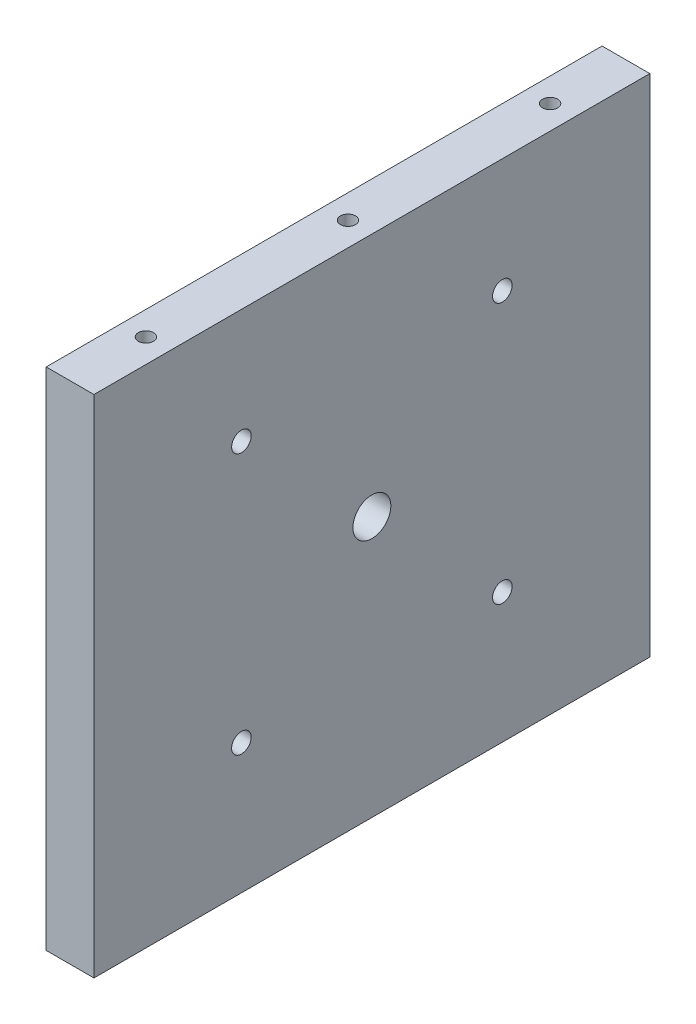
SolidWorks part; units mm, degrees
ref_plane "Front Plane" through (0, 0, 0) normal (0, 0, 1) x (1, 0, 0)
ref_plane "Top Plane" through (0, 0, 0) normal (0, 1, 0) x (1, 0, 0)
ref_plane "Right Plane" through (0, 0, 0) normal (1, 0, 0) x (0, 0, -1)
sketch "Sketch1" plane through (0, 0, 0) normal (1, 0, 0) x (0, 0, -1)
  line L1 (-69.85, -63.5) -> (69.85, -63.5)
  line L2 (-69.85, -63.5) -> (-69.85, 63.5)
  line L3 (-69.85, 63.5) -> (69.85, 63.5)
  line L4 (69.85, -63.5) -> (69.85, 63.5)
  line L5 (-69.85, -63.5) -> (69.85, 63.5) construction
  line L6 (-69.85, 63.5) -> (69.85, -63.5) construction
  point P0 (0, 0)
  dimension "D1" = 139.7
  dimension "D2" = 127
extrude "Boss-Extrude1" add sketch "Sketch1" along normal blind 12
sketch "Sketch2" plane through (0, 0, 0) normal (-1, 0, 0) x (0, 0, 1)
  line L0 (-69.85, 1.97) -> (69.85, 1.97) construction
  line L1 (-32.7869, -30.8169) -> (32.7869, -30.8169)
  line L2 (-32.7869, -30.8169) -> (-32.7869, 34.7569)
  line L3 (-32.7869, 34.7569) -> (32.7869, 34.7569)
  line L4 (32.7869, -30.8169) -> (32.7869, 34.7569)
  line L5 (-32.7869, -30.8169) -> (32.7869, 34.7569) construction
  line L6 (-32.7869, 34.7569) -> (32.7869, -30.8169) construction
  line L7 (-69.85, -63.5) -> (-69.85, 63.5) construction
  line L8 (69.85, 63.5) -> (69.85, -63.5) construction
  circle A0 centre (0, 1.97) radius 43.18
  circle A1 centre (0, 1.97) radius 4.7625
  point P0 (0, -43.7423)
  point P6 (0, 1.97)
  point P7 (-32.7869, 34.7569)
  point P8 (32.7869, 34.7569)
  point P9 (32.7869, -30.8169)
  point P10 (-32.7869, -30.8169)
  dimension "D2" = 86.36
  dimension "D4" = 65.47
  dimension "D5" = 9.525
  dimension "D1" = 92.7354
  dimension "D3" = 90
hole_wizard "#8 Clearance Hole1" positions "Sketch3" profile "Sketch4" hole size "#8" standard "ANSI Inch" end condition through all
sketch "Sketch3" plane through (0, 0, 0) normal (-1, 0, 0) x (0, 0, 1)
  point P0 (-32.7869, 34.7569)
  point P3 (32.7869, 34.7569)
  point P6 (32.7869, -30.8169)
  point P9 (-32.7869, -30.8169)
sketch "Sketch4" plane through (0, 34.7569, -32.7869) normal (0, 1, 0) x (0, 0, 1)
  line L0 (0, 0) -> (0, 12)
  line L1 (0, 12) -> (2.4574, 12)
  line L2 (2.4574, 12) -> (2.4574, 0)
  line L5 (2.4574, 0) -> (0, 0)
  line L11 (0, -6.35) -> (0, 107.95) construction
  dimension "Thru Hole Dia." = 4.9149
  dimension "Thru Hole Depth" = 12
extrude "Cut-Extrude1" cut sketch "Sketch2" against normal blind 1.27 contours L2 A0 | L4 A0 L3 L2 L1 | L3 A0 | L4 A0 | L1 A0 region at (0, -27.9071, -29.8771) region at (0, -35.0203, 0) region at (0, 1.97, -36.9903) region at (0, 1.97, 36.9903) region at (0, 38.9603, 0)
extrude "Cut-Extrude2" cut sketch "Sketch2<4>" against normal through all contours A1 region at (0, 1.97, 0)
sketch "Sketch2<4>" plane through (0, 0, 0) normal (-1, 0, 0) x (0, 0, 1) same geometry as "Sketch2"
sketch "Sketch5" plane through (0, -63.5, 0) normal (0, -1, 0) x (1, 0, 0)
  line L0 (6, 69.85) -> (6, -69.85) construction
  line L1 (12, 69.85) -> (0, 69.85) construction
  line L2 (12, -69.85) -> (0, -69.85) construction
  point P6 (6, 50.8)
  point P7 (6, 0)
  point P8 (6, -50.8)
  dimension "D1" = 19.05
  dimension "D2" = 19.05
hole_wizard "Tap Drill for #10-24 Tap1" positions "Sketch6" profile "Sketch7" hole size "#10-24" standard "ANSI Inch"
sketch "Sketch6" plane through (0, -63.5, 0) normal (0, -1, 0) x (-1, 0, 0)
  line L0 (-6, -69.85) -> (-6, 69.85) construction
  point P0 (-6, 50.8)
  point P3 (-6, 0)
  point P7 (-6, -50.8)
sketch "Sketch7" plane through (6, -63.5, -50.8) normal (1, 0, 0) x (0, 0, -1)
  line L0 (0, 0) -> (0, 13.8408)
  line L1 (0, 13.8408) -> (1.8986, 12.7)
  line L2 (1.8986, 12.7) -> (1.8986, 0)
  line L5 (1.8986, 0) -> (0, 0)
  line L10 (0, 13.8408) -> (-1.8987, 12.7) construction
  line L11 (0, -6.35) -> (0, 107.95) construction
  dimension "Hole Dia." = 3.7973
  dimension "Hole Depth" = 12.7
  dimension "Drill Angle" = 118
ref_plane "Plane1" through (0, 0, 0) normal (0, 1, 0) x (1, 0, 0)
mirror "Mirror1" about plane through (0, 0, 0) normal (0, 1, 0) of "Tap Drill for #10-24 Tap1"
sketch "Sketch8" plane through (1.27, 0, 0) normal (-1, 0, 0) x (0, 0, 1)
  circle A0 centre (0, 1.97) radius 5.715
  dimension "D1" = 11.43
extrude "Cut-Extrude3" cut sketch "Sketch8" against normal blind 0.889
